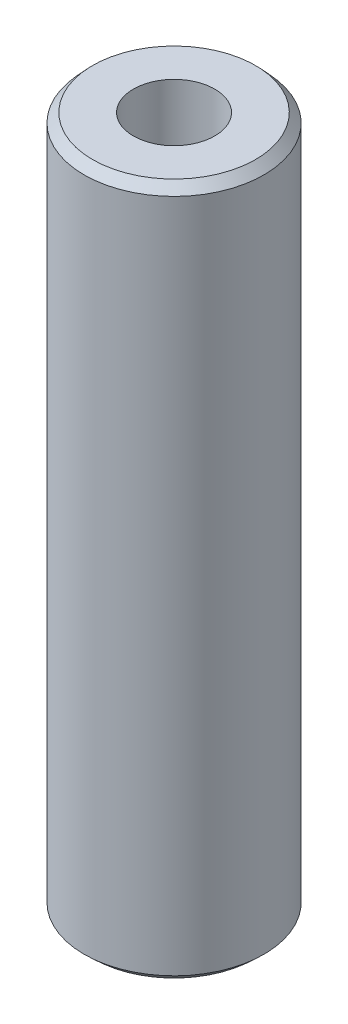
SolidWorks part; units mm, degrees
ref_plane "Front Plane" through (0, 0, 0) normal (0, 0, 1) x (1, 0, 0)
ref_plane "Top Plane" through (0, 0, 0) normal (0, 1, 0) x (1, 0, 0)
ref_plane "Right Plane" through (0, 0, 0) normal (1, 0, 0) x (0, 0, -1)
sketch "Sketch1" plane through (0, 0, 0) normal (0, 1, 0) x (1, 0, 0)
  circle A0 centre (0, 0) radius 42.5
  dimension "SHAFT_OD" = 85
extrude "Boss-Extrude1" add sketch "Sketch1" along normal blind 327.4038
sketch "Sketch2" plane through (0, 0, 0) normal (0, 1, 0) x (1, 0, 0)
  circle A0 centre (0, 0) radius 19.2276
  dimension "BORE_D" = 38.4552
extrude "Cut-Extrude1" cut sketch "Sketch2" along normal through all
chamfer "Chamfer1" distance 4.3003 angle 42.702 2 edges at (0, 327.4038, 42.5) (0, 0, 42.5) first distance on face at (0, 327.4038, 42.5) first distance on face at (0, 0, 19.2276)
